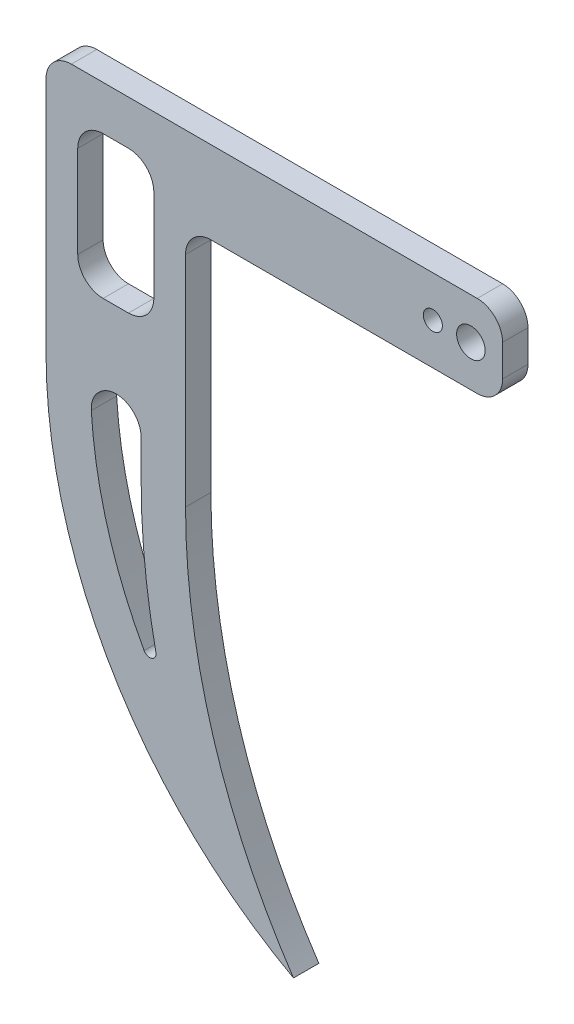
SolidWorks part; units mm, degrees
ref_plane "Plan de face" through (0, 0, 0) normal (0, 0, 1) x (1, 0, 0)
ref_plane "Plan de dessus" through (0, 0, 0) normal (0, 1, 0) x (1, 0, 0)
ref_plane "Plan de droite" through (0, 0, 0) normal (1, 0, 0) x (0, 0, -1)
sketch "Esquisse1" plane through (0, 0, 0) normal (0, 0, 1) x (1, 0, 0)
  line L0 (-11, 18.25) -> (-11, -91.75) construction
  line L1 (-6, -11.25) -> (6, -11.25)
  line L2 (-6, -11.25) -> (-6, 11.25)
  line L3 (-6, 11.25) -> (6, 11.25)
  line L4 (6, -11.25) -> (6, 11.25)
  line L5 (-6, -11.25) -> (6, 11.25) construction
  line L6 (-6, 11.25) -> (6, -11.25) construction
  line L8 (-11, -18.25) -> (-11, 18.25)
  line L9 (-11, 18.25) -> (11, 18.25)
  line L10 (11, -18.25) -> (11, 18.25)
  line L11 (-11, -18.25) -> (11, 18.25) construction
  line L12 (-11, 18.25) -> (11, -18.25) construction
  line L14 (11, -18.25) -> (11, -33.25)
  line L16 (-11, -18.25) -> (-11, -23.25)
  arc A0 (-11, -23.25) -> (28.02, -89.0561) centre (64, -23.25) ccw
  arc A1 (11, -33.25) -> (28.02, -89.0561) centre (111, -33.25) ccw
  point P0 (0, 0)
  point P6 (0, 0)
  point P16 (28.02, -89.0561)
  dimension "D5" = 5
  dimension "D6" = 200
  dimension "D7" = 150
  dimension "D8" = 110
  dimension "D1" = 12
  dimension "D2" = 22.5
  dimension "D3" = 7
  dimension "D4" = 5
  dimension "D9" = 15
  dimension "D10" = 5
extrude "Boss.-Extru.1" add sketch "Esquisse1" along normal blind 4
sketch "Esquisse2" plane through (0, 0, 4) normal (0, 0, 1) x (1, 0, 0)
  line L0 (-4, -23.25) -> (4, -23.25)
  line L1 (4, -23.25) -> (4, -33.25)
  arc A4 (4, -33.25) -> (7.8093, -61.5463) centre (111, -33.25) ccw
  arc A5 (-4, -23.25) -> (7.8093, -61.5463) centre (64, -23.25) ccw
  arc A6 (4, -33.25) -> (7.8093, -61.5463) centre (111, -33.25) ccw
  arc A7 (-4, -23.25) -> (7.8093, -61.5463) centre (64, -23.25) ccw
  dimension "D1" = 7
extrude "Enlèv. mat.-Extru.1" cut sketch "Esquisse2" against normal through all
sketch "Sketch1" plane through (0, 0, 4) normal (0, 0, 1) x (1, 0, 0)
  line L0 (11, 18.25) -> (61, 18.25)
  line L1 (61, 18.25) -> (61, 5.25)
  line L2 (61, 5.25) -> (11, 5.25)
  line L3 (11, -33.25) -> (11, 18.25) construction
  line L4 (11, 5.25) -> (11, 18.25)
  dimension "D1" = 13
  dimension "D2" = 50
extrude "Boss-Extrude1" add sketch "Sketch1" against normal blind 4
sketch "Sketch2" plane through (0, 0, 4) normal (0, 0, 1) x (1, 0, 0)
  line L0 (61, 5.25) -> (61, 18.25) construction
  circle A0 centre (56, 11.75) radius 2.25
  circle A1 centre (50, 11.75) radius 1.5
  point P5 (61, 11.75)
  point P7 (0, 0)
  point P10 (0, 0)
  dimension "D1" = 4.5
  dimension "D3" = 3
  dimension "D2" = 5
  dimension "D4" = 6
extrude "Cut-Extrude1" cut sketch "Sketch2" against normal up to surface (4 mm away) up to face at (1.994, -35.5784, 0)
fillet "Fillet1" radius 4 10 edges at (11, 5.25, 2) (-11, 18.25, 2) (61, 5.25, 2) (61, 18.25, 2) (4, -23.25, 2) (-4, -23.25, 2) (6, -11.25, 2) (-6, -11.25, 2) (6, 11.25, 2) (-6, 11.25, 2)
fillet "Fillet2" radius 1 1 edges at (7.8093, -61.5463, 2)
